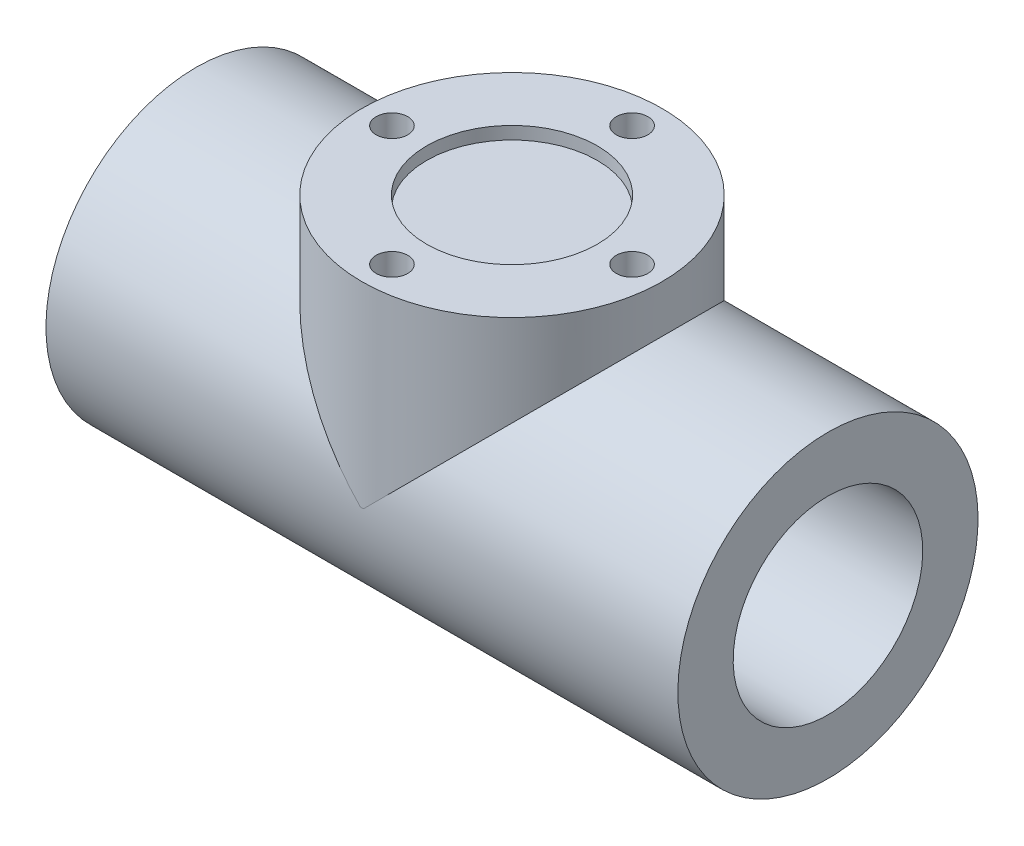
SolidWorks part; units mm, degrees
ref_plane "Front Plane" through (0, 0, 0) normal (0, 0, 1) x (1, 0, 0)
ref_plane "Top Plane" through (0, 0, 0) normal (0, 1, 0) x (1, 0, 0)
ref_plane "Right Plane" through (0, 0, 0) normal (1, 0, 0) x (0, 0, -1)
sketch "Sketch1" plane through (0, 0, 0) normal (0, 0, 1) x (1, 0, 0)
  line L0 (-100, 0) -> (-100, 47.5)
  line L1 (-100, 47.5) -> (100, 47.5)
  line L2 (100, 47.5) -> (100, 0)
  line L3 (100, 0) -> (-100, 0)
  dimension "D1" = 200
  dimension "D2" = 100
  dimension "D3" = 47.5
revolve "Revolve1" add sketch "Sketch1" angle 360 about L3
ref_plane "Plane1" through (0, 62.5, 0) normal (0, 1, 0) x (1, 0, 0)
sketch "Sketch2" plane through (0, 62.5, 0) normal (0, 1, 0) x (1, 0, 0)
  circle A0 centre (0, 0) radius 47.5
  dimension "D1" = 95
extrude "Boss-Extrude1" add sketch "Sketch2" against normal blind 62
sketch "Sketch3" plane through (0, 62.5, 0) normal (0, 1, 0) x (1, 0, 0)
  circle A0 centre (0, 0) radius 27
  dimension "D1" = 54
extrude "Cut-Extrude1" cut sketch "Sketch3" against normal blind 4
sketch "Sketch4" plane through (0, 62.5, 0) normal (0, 1, 0) x (1, 0, 0)
  circle A0 centre (0, 0) radius 38 construction
  point P4 (0, 38)
  dimension "D1" = 76
hole_wizard "Ø1.0mm Dowel Hole1" positions "Sketch4" profile "Sketch5" hole size "Ø1.0" standard "ISO"
sketch "Sketch5" plane through (0, 62.5, -38) normal (1, 0, 0) x (0, 0, 1)
  line L0 (0, 0) -> (0, 23.0043)
  line L1 (0, 23.0043) -> (5, 20)
  line L2 (5, 20) -> (5, 0)
  line L5 (5, 0) -> (0, 0)
  line L10 (0, 23.0043) -> (-5, 20) construction
  line L11 (0, -6.35) -> (0, 107.95) construction
  dimension "Hole Dia." = 10
  dimension "Hole Depth" = 20
  dimension "Drill Angle" = 118
pattern_circular "CirPattern1" count 4 over 360 about axis through (0, 62.5, 0) along (0, 1, 0) of "Ø1.0mm Dowel Hole1"
sketch "Sketch6" plane through (100, 0, 0) normal (1, 0, 0) x (0, 0, -1)
  circle A0 centre (0, 0) radius 30
  dimension "D1" = 60
extrude "Cut-Extrude2" cut sketch "Sketch6" against normal through all
